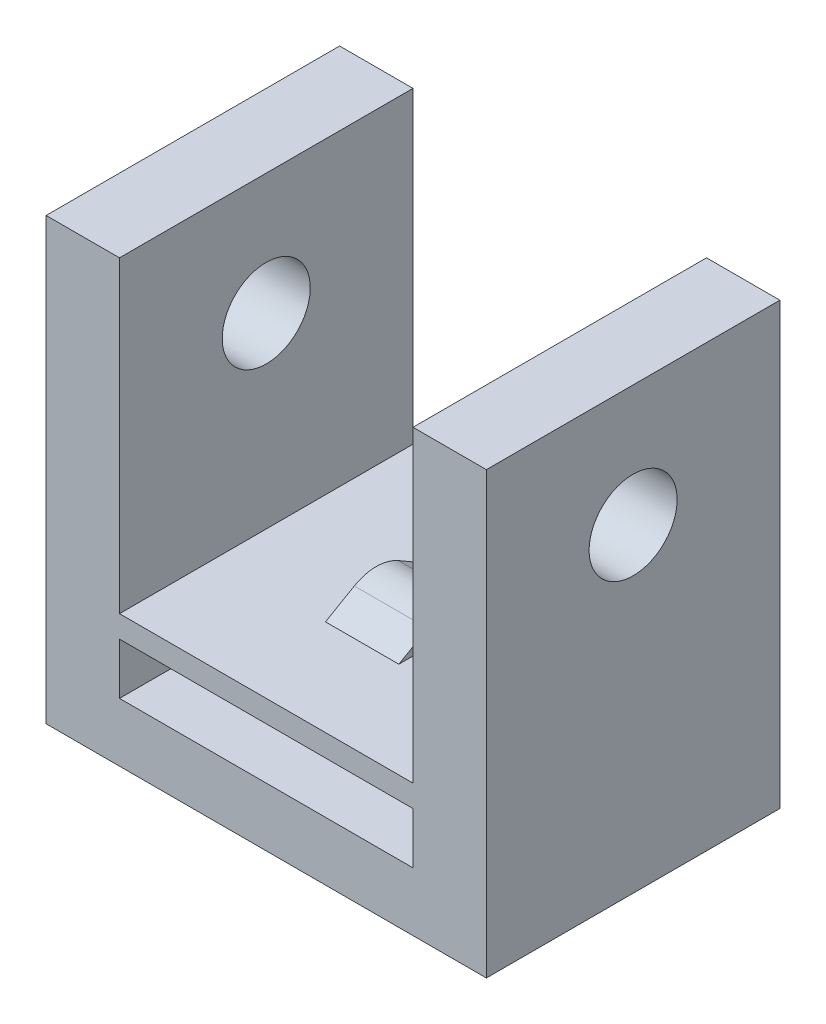
SolidWorks part; units mm, degrees
ref_plane "Front Plane" through (0, 0, 0) normal (0, 0, 1) x (1, 0, 0)
ref_plane "Top Plane" through (0, 0, 0) normal (0, 1, 0) x (1, 0, 0)
ref_plane "Right Plane" through (0, 0, 0) normal (1, 0, 0) x (0, 0, -1)
sketch "Sketch1" plane through (0, 0, 0) normal (0, 0, 1) x (1, 0, 0)
  line L1 (-7.3312, 6.8625) -> (7.6688, 6.8625)
  line L2 (-7.3312, 6.8625) -> (-7.3312, -8.1375)
  line L3 (-7.3312, -8.1375) -> (7.6688, -8.1375)
  line L4 (7.6688, 6.8625) -> (7.6688, -8.1375)
  line L5 (-4.8312, 6.8625) -> (5.1688, 6.8625)
  line L6 (-4.8312, 6.8625) -> (-4.8312, -3.6375)
  line L7 (-4.8312, -3.6375) -> (5.1688, -3.6375)
  line L8 (5.1688, 6.8625) -> (5.1688, -3.6375)
  line L9 (-4.8312, -3.6375) -> (5.1688, -3.6375)
  line L10 (-4.8312, -3.6375) -> (-4.8312, -4.3875)
  line L11 (-4.8312, -4.3875) -> (5.1688, -4.3875)
  line L12 (5.1688, -3.6375) -> (5.1688, -4.3875)
  line L13 (5.1688, -4.3875) -> (-4.8312, -4.3875)
  line L14 (5.1688, -4.3875) -> (5.1688, -6.1375)
  line L15 (5.1688, -6.1375) -> (-4.8312, -6.1375)
  line L16 (-4.8312, -4.3875) -> (-4.8312, -6.1375)
  point P13 (-4.8312, -6.4968)
  dimension "D1" = 15
  dimension "D2" = 15
  dimension "D3" = 10
  dimension "D4" = 2.5
  dimension "D5" = 10.5
  dimension "D6" = 0.75
  dimension "D7" = 1.75
extrude "Boss-Extrude1" add sketch "Sketch1" along normal blind 10 contours L16 L10 L6 L1 L2 L3 L4 L8 L12 L14 L15 | L12 L7 L10 L11 region at (-6.0812, 6.6504, 0) region at (0.1688, -4.0125, 0)
ref_plane "Plane1" through (0.1688, 0, 0) normal (1, 0, 0) x (0, 0, -1)
sketch "Sketch2" plane through (0.1688, 0, 0) normal (1, 0, 0) x (0, 0, -1)
  line L0 (-6.7321, -3.6375) -> (-5, -2.6375)
  line L1 (-5, -2.6375) -> (-3.2679, -3.6375)
  line L4 (0, -3.6375) -> (0, 6.8625)
  line L5 (0, 6.8625) -> (-10, 6.8625)
  line L6 (-10, 6.8625) -> (-10, -3.6375)
  line L7 (-10, -3.6375) -> (0, -3.6375)
  line L8 (0, -3.6375) -> (0, 6.8625)
  line L9 (0, 6.8625) -> (-10, 6.8625)
  line L10 (-10, 6.8625) -> (-10, -3.6375)
  line L11 (-10, -3.6375) -> (0, -3.6375)
  circle A0 centre (-5, 2.7306) radius 1.5
  dimension "D6" = 3
  dimension "D2" = 5
  dimension "D3" = 2
  dimension "D4" = 2
  dimension "D5" = 30
  dimension "D1" = 0
extrude "Boss-Extrude2" add sketch "Sketch2" along normal mid plane 2.5 contours L0 L11 L1 region at (0.1688, -3.3042, 5)
extrude "Cut-Extrude1" cut sketch "Sketch2<5>" against normal mid plane 50 contours A0 region at (0.1688, 2.7306, 5)
sketch "Sketch2<5>" plane through (0.1688, 0, 0) normal (1, 0, 0) x (0, 0, -1) same geometry as "Sketch2"
fillet "Fillet1" radius 1.5 1 edges at (0.1688, -2.6375, 5)
